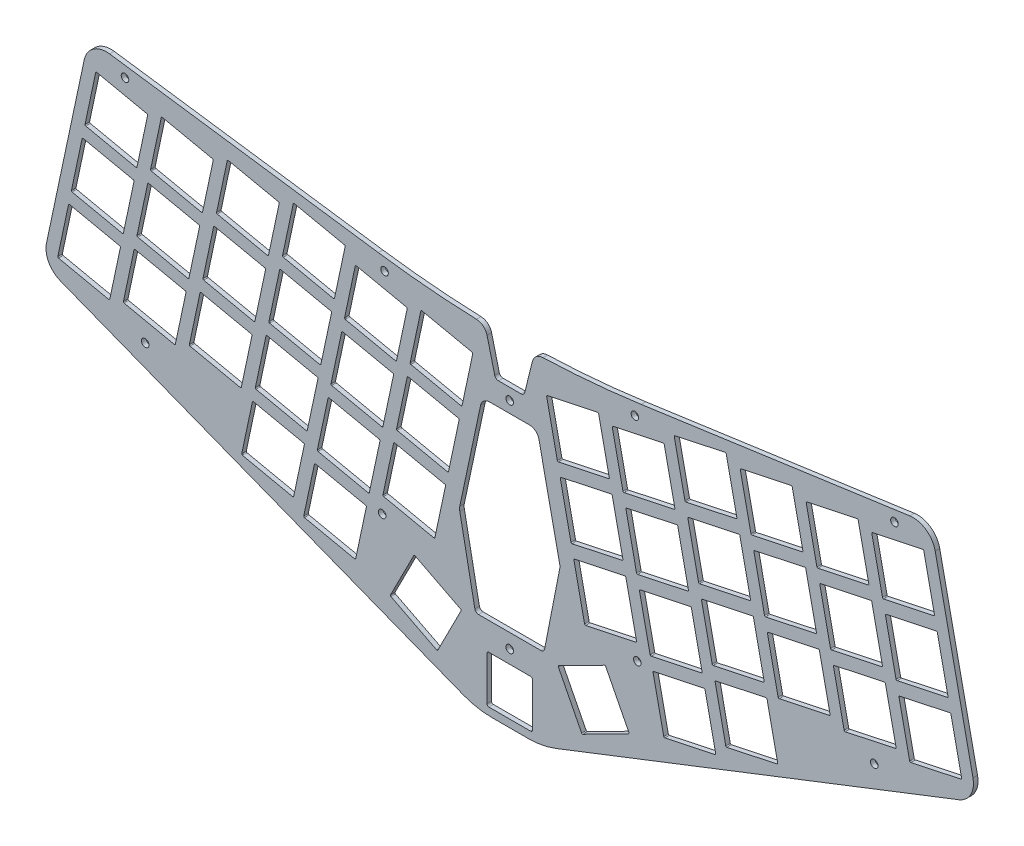
SolidWorks part; units mm, degrees
ref_plane "Front Plane" through (0, 0, 0) normal (0, 0, 1) x (1, 0, 0)
ref_plane "Top Plane" through (0, 0, 0) normal (0, 1, 0) x (1, 0, 0)
ref_plane "Right Plane" through (0, 0, 0) normal (1, 0, 0) x (0, 0, -1)
sketch "Model" plane through (0, 0, 0) normal (0, 0, 1) x (1, 0, 0)
  line L0 (118.9761, -36.3417) -> (119.3386, -36.3417)
  line L1 (109.9761, -36.3417) -> (109.6135, -36.3417)
  line L2 (130.2178, -33.5671) -> (126.6009, -34.9766)
  line L3 (98.7344, -33.5671) -> (102.3512, -34.9766)
  line L4 (114.4761, -36.3417) -> (109.9761, -36.3417)
  line L5 (114.4761, -36.3417) -> (118.9761, -36.3417)
  line L6 (118.4251, 42.1791) -> (120.4508, 50.3035)
  line L7 (110.527, 42.1791) -> (108.5014, 50.3035)
  line L8 (130.2178, -33.5671) -> (232.9153, 6.4558)
  line L9 (236.6055, 13.2938) -> (226.6558, 60.1035)
  line L10 (219.9519, 64.7976) -> (149.1302, 54.8443)
  line L11 (79.822, 54.8443) -> (9.0003, 64.7976)
  line L12 (2.2964, 60.1035) -> (-7.6533, 13.2938)
  line L13 (-3.9631, 6.4558) -> (98.7344, -33.5671)
  line L14 (111.4973, 41.421) -> (117.4548, 41.421)
  line L15 (119.9761, -34.3417) -> (108.9761, -34.3417)
  line L16 (120.4761, -22.3417) -> (120.4761, -33.8417)
  line L17 (108.9761, -21.8417) -> (119.9761, -21.8417)
  line L18 (108.4761, -33.8417) -> (108.4761, -22.3417)
  line L19 (123.6714, -13.7578) -> (127.6435, 6.5155)
  line L20 (105.2808, -13.7578) -> (101.3087, 6.5155)
  line L21 (106.2621, -14.5655) -> (122.69, -14.5655)
  line L22 (109.4761, 35.421) -> (109.2316, 35.421)
  line L23 (119.4761, 35.421) -> (119.7205, 35.421)
  line L24 (109.4761, 35.421) -> (119.4761, 35.421)
  line L25 (127.6339, 7.716) -> (122.1659, 33.4408)
  line L26 (101.3183, 7.716) -> (106.7863, 33.4408)
  line L27 (230.5128, 25.1235) -> (217.3078, 22.3167)
  line L28 (217.1153, 22.0202) -> (219.9221, 8.8152)
  line L29 (220.2186, 8.6226) -> (233.4236, 11.4294)
  line L30 (233.6161, 11.7259) -> (230.8093, 24.9309)
  line L31 (226.9263, 41.9965) -> (213.7213, 39.1897)
  line L32 (213.5288, 38.8932) -> (216.3356, 25.6882)
  line L33 (216.6321, 25.4957) -> (229.8371, 28.3025)
  line L34 (230.0297, 28.599) -> (227.2228, 41.804)
  line L35 (223.3399, 58.8696) -> (210.1349, 56.0628)
  line L36 (209.9423, 55.7663) -> (212.7491, 42.5613)
  line L37 (213.0456, 42.3687) -> (226.2506, 45.1755)
  line L38 (226.4432, 45.472) -> (223.6364, 58.677)
  line L39 (213.2239, 23.4933) -> (200.0189, 20.6865)
  line L40 (199.8264, 20.39) -> (202.6332, 7.185)
  line L41 (202.9297, 6.9924) -> (216.1347, 9.7992)
  line L42 (216.3273, 10.0958) -> (213.5205, 23.3007)
  line L43 (209.6375, 40.3663) -> (196.4325, 37.5595)
  line L44 (196.2399, 37.263) -> (199.0467, 24.058)
  line L45 (199.3432, 23.8655) -> (212.5482, 26.6723)
  line L46 (212.7408, 26.9688) -> (209.934, 40.1738)
  line L47 (206.051, 57.2394) -> (192.846, 54.4326)
  line L48 (192.6534, 54.1361) -> (195.4602, 40.9311)
  line L49 (195.7568, 40.7385) -> (208.9618, 43.5453)
  line L50 (209.1543, 43.8418) -> (206.3475, 57.0468)
  line L51 (195.8311, 22.3522) -> (182.6261, 19.5454)
  line L52 (182.4336, 19.2489) -> (185.2404, 6.0439)
  line L53 (185.5369, 5.8513) -> (198.7419, 8.6581)
  line L54 (198.9344, 8.9546) -> (196.1276, 22.1596)
  line L55 (192.2446, 39.2252) -> (179.0396, 36.4184)
  line L56 (178.8471, 36.1219) -> (181.6539, 22.9169)
  line L57 (181.9504, 22.7244) -> (195.1554, 25.5312)
  line L58 (195.348, 25.8277) -> (192.5412, 39.0327)
  line L59 (188.6582, 56.0983) -> (175.4532, 53.2915)
  line L60 (175.2606, 52.995) -> (178.0674, 39.79)
  line L61 (178.3639, 39.5974) -> (191.5689, 42.4042)
  line L62 (191.7615, 42.7007) -> (188.9547, 55.9057)
  line L63 (182.0248, 4.338) -> (168.8198, 1.5312)
  line L64 (168.6272, 1.2347) -> (171.434, -11.9703)
  line L65 (171.7305, -12.1628) -> (184.9355, -9.356)
  line L66 (185.1281, -9.0595) -> (182.3213, 4.1455)
  line L67 (178.4383, 21.2111) -> (165.2333, 18.4043)
  line L68 (165.0407, 18.1078) -> (167.8475, 4.9028)
  line L69 (168.1441, 4.7102) -> (181.3491, 7.517)
  line L70 (181.5416, 7.8135) -> (178.7348, 21.0185)
  line L71 (174.8518, 38.0841) -> (161.6468, 35.2773)
  line L72 (161.4543, 34.9808) -> (164.2611, 21.7758)
  line L73 (164.5576, 21.5833) -> (177.7626, 24.3901)
  line L74 (177.9551, 24.6866) -> (175.1483, 37.8916)
  line L75 (171.2653, 54.9572) -> (158.0603, 52.1504)
  line L76 (157.8678, 51.8539) -> (160.6746, 38.6489)
  line L77 (160.9711, 38.4563) -> (174.1761, 41.2631)
  line L78 (174.3687, 41.5596) -> (171.5619, 54.7646)
  line L79 (165.6715, -1.6938) -> (152.4665, -4.5006)
  line L80 (152.2739, -4.7971) -> (155.0808, -18.0021)
  line L81 (155.3773, -18.1947) -> (168.5823, -15.3879)
  line L82 (168.7748, -15.0914) -> (165.968, -1.8864)
  line L83 (162.085, 15.1792) -> (148.88, 12.3724)
  line L84 (148.6875, 12.0759) -> (151.4943, -1.1291)
  line L85 (151.7908, -1.3216) -> (164.9958, 1.4852)
  line L86 (165.1883, 1.7817) -> (162.3815, 14.9867)
  line L87 (158.4985, 32.0523) -> (145.2936, 29.2455)
  line L88 (145.101, 28.949) -> (147.9078, 15.744)
  line L89 (148.2043, 15.5514) -> (161.4093, 18.3582)
  line L90 (161.6019, 18.6547) -> (158.7951, 31.8597)
  line L91 (154.9121, 48.9253) -> (141.7071, 46.1185)
  line L92 (141.5145, 45.822) -> (144.3213, 32.617)
  line L93 (144.6178, 32.4245) -> (157.8228, 35.2313)
  line L94 (158.0154, 35.5278) -> (155.2086, 48.7328)
  line L95 (137.6232, 47.2952) -> (124.4182, 44.4883)
  line L96 (124.2256, 44.1918) -> (127.0325, 30.9868)
  line L97 (127.329, 30.7943) -> (140.534, 33.6011)
  line L98 (140.7265, 33.8976) -> (137.9197, 47.1026)
  line L99 (141.2097, 30.4221) -> (128.0047, 27.6153)
  line L100 (127.8121, 27.3188) -> (130.6189, 14.1138)
  line L101 (130.9154, 13.9212) -> (144.1204, 16.728)
  line L102 (144.313, 17.0246) -> (141.5062, 30.2295)
  line L103 (144.7962, 13.5491) -> (131.5912, 10.7423)
  line L104 (131.3986, 10.4457) -> (134.2054, -2.7593)
  line L105 (134.5019, -2.9518) -> (147.7069, -0.145)
  line L106 (147.8995, 0.1515) -> (145.0927, 13.3565)
  line L107 (139.4422, -9.5606) -> (127.4136, -15.6895)
  line L108 (127.3043, -16.0257) -> (133.4332, -28.0543)
  line L109 (133.7695, -28.1635) -> (145.7981, -22.0347)
  line L110 (145.9073, -21.6984) -> (139.7784, -9.6698)
  line L111 (101.5386, -15.6895) -> (89.51, -9.5606)
  line L112 (89.1737, -9.6698) -> (83.0449, -21.6984)
  line L113 (83.1541, -22.0347) -> (95.1827, -28.1635)
  line L114 (95.519, -28.0543) -> (101.6478, -16.0257)
  line L115 (97.361, 10.7423) -> (84.156, 13.5491)
  line L116 (83.8595, 13.3565) -> (81.0527, 0.1515)
  line L117 (81.2453, -0.145) -> (94.4502, -2.9518)
  line L118 (94.7468, -2.7593) -> (97.5536, 10.4457)
  line L119 (100.9475, 27.6153) -> (87.7425, 30.4221)
  line L120 (87.446, 30.2295) -> (84.6392, 17.0246)
  line L121 (84.8317, 16.728) -> (98.0367, 13.9212)
  line L122 (98.3332, 14.1138) -> (101.14, 27.3188)
  line L123 (104.534, 44.4883) -> (91.329, 47.2952)
  line L124 (91.0325, 47.1026) -> (88.2256, 33.8976)
  line L125 (88.4182, 33.6011) -> (101.6232, 30.7943)
  line L126 (101.9197, 30.9868) -> (104.7265, 44.1918)
  line L127 (76.4857, -4.5006) -> (63.2807, -1.6938)
  line L128 (62.9842, -1.8864) -> (60.1773, -15.0914)
  line L129 (60.3699, -15.3879) -> (73.5749, -18.1947)
  line L130 (73.8714, -18.0021) -> (76.6782, -4.7971)
  line L131 (80.0721, 12.3724) -> (66.8671, 15.1792)
  line L132 (66.5706, 14.9867) -> (63.7638, 1.7817)
  line L133 (63.9564, 1.4852) -> (77.1614, -1.3216)
  line L134 (77.4579, -1.1291) -> (80.2647, 12.0759)
  line L135 (83.6586, 29.2455) -> (70.4536, 32.0523)
  line L136 (70.1571, 31.8597) -> (67.3503, 18.6547)
  line L137 (67.5429, 18.3582) -> (80.7479, 15.5514)
  line L138 (81.0444, 15.744) -> (83.8512, 28.949)
  line L139 (87.2451, 46.1185) -> (74.0401, 48.9253)
  line L140 (73.7436, 48.7328) -> (70.9368, 35.5278)
  line L141 (71.1293, 35.2313) -> (84.3343, 32.4245)
  line L142 (84.6308, 32.617) -> (87.4377, 45.822)
  line L143 (60.1324, 1.5312) -> (46.9274, 4.338)
  line L144 (46.6309, 4.1455) -> (43.8241, -9.0595)
  line L145 (44.0166, -9.356) -> (57.2216, -12.1628)
  line L146 (57.5181, -11.9703) -> (60.325, 1.2347)
  line L147 (63.7189, 18.4043) -> (50.5139, 21.2111)
  line L148 (50.2174, 21.0185) -> (47.4106, 7.8135)
  line L149 (47.6031, 7.517) -> (60.8081, 4.7102)
  line L150 (61.1046, 4.9028) -> (63.9114, 18.1078)
  line L151 (67.3054, 35.2773) -> (54.1004, 38.0841)
  line L152 (53.8038, 37.8916) -> (50.997, 24.6866)
  line L153 (51.1896, 24.3901) -> (64.3946, 21.5833)
  line L154 (64.6911, 21.7758) -> (67.4979, 34.9808)
  line L155 (70.8918, 52.1504) -> (57.6868, 54.9572)
  line L156 (57.3903, 54.7646) -> (54.5835, 41.5596)
  line L157 (54.7761, 41.2631) -> (67.9811, 38.4563)
  line L158 (68.2776, 38.6489) -> (71.0844, 51.8539)
  line L159 (46.5186, 19.2489) -> (45.1152, 12.6464)
  line L160 (33.1211, 22.3522) -> (46.326, 19.5454)
  line L161 (30.0177, 8.9546) -> (32.8245, 22.1596)
  line L162 (43.4153, 5.8513) -> (30.2103, 8.6581)
  line L163 (45.1152, 12.6464) -> (43.7118, 6.0439)
  line L164 (50.1051, 36.1219) -> (48.7017, 29.5194)
  line L165 (36.7075, 39.2252) -> (49.9125, 36.4184)
  line L166 (33.6042, 25.8277) -> (36.411, 39.0327)
  line L167 (47.0018, 22.7244) -> (33.7968, 25.5312)
  line L168 (48.7017, 29.5194) -> (47.2983, 22.9169)
  line L169 (53.6916, 52.995) -> (52.2882, 46.3925)
  line L170 (40.294, 56.0983) -> (53.499, 53.2915)
  line L171 (37.1907, 42.7007) -> (39.9975, 55.9057)
  line L172 (50.5882, 39.5974) -> (37.3832, 42.4042)
  line L173 (52.2882, 46.3925) -> (50.8848, 39.79)
  line L174 (29.1258, 20.39) -> (27.7224, 13.7875)
  line L175 (15.7282, 23.4933) -> (28.9332, 20.6865)
  line L176 (12.6249, 10.0958) -> (15.4317, 23.3007)
  line L177 (26.0225, 6.9924) -> (12.8175, 9.7992)
  line L178 (27.7224, 13.7875) -> (26.319, 7.185)
  line L179 (32.7123, 37.263) -> (31.3089, 30.6605)
  line L180 (19.3147, 40.3663) -> (32.5197, 37.5595)
  line L181 (16.2114, 26.9688) -> (19.0182, 40.1738)
  line L182 (29.6089, 23.8655) -> (16.4039, 26.6723)
  line L183 (31.3089, 30.6605) -> (29.9055, 24.058)
  line L184 (19.7979, 43.8418) -> (21.2013, 50.4443)
  line L185 (33.1954, 40.7385) -> (19.9904, 43.5453)
  line L186 (36.2987, 54.1361) -> (33.4919, 40.9311)
  line L187 (22.9012, 57.2394) -> (36.1062, 54.4326)
  line L188 (21.2013, 50.4443) -> (22.6047, 57.0468)
  line L189 (-4.664, 11.7259) -> (-3.2606, 18.3284)
  line L190 (8.7336, 8.6226) -> (-4.4714, 11.4294)
  line L191 (11.8369, 22.0202) -> (9.0301, 8.8152)
  line L192 (-1.5606, 25.1235) -> (11.6444, 22.3167)
  line L193 (-3.2606, 18.3284) -> (-1.8572, 24.9309)
  line L194 (15.2308, 39.1897) -> (8.6283, 40.5931)
  line L195 (12.6166, 25.6882) -> (15.4234, 38.8932)
  line L196 (-0.8849, 28.3025) -> (12.3201, 25.4957)
  line L197 (1.7293, 41.804) -> (-1.0775, 28.599)
  line L198 (8.6283, 40.5931) -> (2.0258, 41.9965)
  line L199 (2.509, 45.472) -> (3.9124, 52.0745)
  line L200 (15.9065, 42.3687) -> (2.7016, 45.1755)
  line L201 (19.0099, 55.7663) -> (16.2031, 42.5613)
  line L202 (5.6123, 58.8696) -> (18.8173, 56.0628)
  line L203 (3.9124, 52.0745) -> (5.3158, 58.677)
  circle A0 centre (215.9057, 61.3788) radius 1
  circle A1 centre (13.0465, 61.3788) radius 1
  circle A2 centre (148.1114, -4.3098) radius 1
  circle A3 centre (80.8407, -4.3098) radius 1
  circle A4 centre (210.5718, 3.5051) radius 1
  circle A5 centre (147.4779, 51.4345) radius 1
  circle A6 centre (81.4742, 51.4345) radius 1
  circle A7 centre (18.3804, 3.5051) radius 1
  circle A8 centre (114.4761, -18.3417) radius 1
  circle A9 centre (114.4761, 38.421) radius 1
  arc A10 (108.4761, -33.8417) -> (108.9761, -34.3417) centre (108.9761, -33.8417) ccw
  arc A11 (119.9761, -34.3417) -> (120.4761, -33.8417) centre (119.9761, -33.8417) ccw
  arc A12 (120.4761, -22.3417) -> (119.9761, -21.8417) centre (119.9761, -22.3417) ccw
  arc A13 (108.9761, -21.8417) -> (108.4761, -22.3417) centre (108.9761, -22.3417) ccw
  arc A14 (122.69, -14.5655) -> (123.6714, -13.7578) centre (122.69, -13.5655) ccw
  arc A15 (105.2808, -13.7578) -> (106.2621, -14.5655) centre (106.2621, -13.5655) ccw
  arc A16 (127.6435, 6.5155) -> (127.6339, 7.716) centre (124.6994, 7.0923) ccw
  arc A17 (101.3183, 7.716) -> (101.3087, 6.5155) centre (104.2527, 7.0923) ccw
  arc A18 (122.1659, 33.4408) -> (119.7205, 35.421) centre (119.7205, 32.921) ccw
  arc A19 (109.2316, 35.421) -> (106.7863, 33.4408) centre (109.2316, 32.921) ccw
  arc A20 (46.5186, 19.2489) -> (46.326, 19.5454) centre (46.2741, 19.3008) ccw
  arc A21 (30.0177, 8.9546) -> (30.2103, 8.6581) centre (30.2623, 8.9027) ccw
  arc A22 (33.1211, 22.3522) -> (32.8245, 22.1596) centre (33.0691, 22.1077) ccw
  arc A23 (43.4153, 5.8513) -> (43.7118, 6.0439) centre (43.4673, 6.0959) ccw
  arc A24 (50.1051, 36.1219) -> (49.9125, 36.4184) centre (49.8605, 36.1739) ccw
  arc A25 (36.7075, 39.2252) -> (36.411, 39.0327) centre (36.6556, 38.9807) ccw
  arc A26 (33.6042, 25.8277) -> (33.7968, 25.5312) centre (33.8487, 25.7757) ccw
  arc A27 (47.0018, 22.7244) -> (47.2983, 22.9169) centre (47.0537, 22.9689) ccw
  arc A28 (53.6916, 52.995) -> (53.499, 53.2915) centre (53.447, 53.0469) ccw
  arc A29 (40.294, 56.0983) -> (39.9975, 55.9057) centre (40.242, 55.8537) ccw
  arc A30 (37.1907, 42.7007) -> (37.3832, 42.4042) centre (37.4352, 42.6488) ccw
  arc A31 (50.5882, 39.5974) -> (50.8848, 39.79) centre (50.6402, 39.8419) ccw
  arc A32 (29.1258, 20.39) -> (28.9332, 20.6865) centre (28.8812, 20.442) ccw
  arc A33 (15.7282, 23.4933) -> (15.4317, 23.3007) centre (15.6763, 23.2488) ccw
  arc A34 (12.6249, 10.0958) -> (12.8175, 9.7992) centre (12.8694, 10.0438) ccw
  arc A35 (26.0225, 6.9924) -> (26.319, 7.185) centre (26.0744, 7.237) ccw
  arc A36 (19.3147, 40.3663) -> (19.0182, 40.1738) centre (19.2627, 40.1218) ccw
  arc A37 (32.7123, 37.263) -> (32.5197, 37.5595) centre (32.4677, 37.315) ccw
  arc A38 (16.2114, 26.9688) -> (16.4039, 26.6723) centre (16.4559, 26.9168) ccw
  arc A39 (29.6089, 23.8655) -> (29.9055, 24.058) centre (29.6609, 24.11) ccw
  arc A40 (19.7979, 43.8418) -> (19.9904, 43.5453) centre (20.0424, 43.7899) ccw
  arc A41 (36.2987, 54.1361) -> (36.1062, 54.4326) centre (36.0542, 54.188) ccw
  arc A42 (33.1954, 40.7385) -> (33.4919, 40.9311) centre (33.2474, 40.9831) ccw
  arc A43 (22.9012, 57.2394) -> (22.6047, 57.0468) centre (22.8492, 56.9949) ccw
  arc A44 (-4.664, 11.7259) -> (-4.4714, 11.4294) centre (-4.4194, 11.674) ccw
  arc A45 (11.8369, 22.0202) -> (11.6444, 22.3167) centre (11.5924, 22.0721) ccw
  arc A46 (8.7336, 8.6226) -> (9.0301, 8.8152) centre (8.7856, 8.8671) ccw
  arc A47 (-1.5606, 25.1235) -> (-1.8572, 24.9309) centre (-1.6126, 24.8789) ccw
  arc A48 (15.4234, 38.8932) -> (15.2308, 39.1897) centre (15.1789, 38.9452) ccw
  arc A49 (12.3201, 25.4957) -> (12.6166, 25.6882) centre (12.372, 25.7402) ccw
  arc A50 (-1.0775, 28.599) -> (-0.8849, 28.3025) centre (-0.8329, 28.547) ccw
  arc A51 (2.0258, 41.9965) -> (1.7293, 41.804) centre (1.9739, 41.752) ccw
  arc A52 (2.509, 45.472) -> (2.7016, 45.1755) centre (2.7535, 45.42) ccw
  arc A53 (19.0099, 55.7663) -> (18.8173, 56.0628) centre (18.7653, 55.8182) ccw
  arc A54 (15.9065, 42.3687) -> (16.2031, 42.5613) centre (15.9585, 42.6132) ccw
  arc A55 (5.6123, 58.8696) -> (5.3158, 58.677) centre (5.5603, 58.625) ccw
  arc A56 (102.3512, -34.9766) -> (109.6135, -36.3417) centre (109.6135, -16.3417) ccw
  arc A57 (119.3386, -36.3417) -> (126.6009, -34.9766) centre (119.3386, -16.3417) ccw
  arc A58 (108.5014, 50.3035) -> (105.6963, 52.5758) centre (105.5905, 49.5777) ccw
  arc A59 (123.2559, 52.5758) -> (120.4508, 50.3035) centre (123.3617, 49.5777) ccw
  arc A60 (117.4548, 41.421) -> (118.4251, 42.1791) centre (117.4548, 42.421) ccw
  arc A61 (110.527, 42.1791) -> (111.4973, 41.421) centre (111.4973, 42.421) ccw
  arc A62 (232.9153, 6.4558) -> (236.6055, 13.2938) centre (230.7366, 12.0463) ccw
  arc A63 (226.6558, 60.1035) -> (219.9519, 64.7976) centre (220.7869, 58.856) ccw
  arc A64 (123.2559, 52.5758) -> (149.1302, 54.8443) centre (114.4761, 301.421) ccw
  arc A65 (79.822, 54.8443) -> (105.6963, 52.5758) centre (114.4761, 301.421) ccw
  arc A66 (9.0003, 64.7976) -> (2.2964, 60.1035) centre (8.1653, 58.856) ccw
  arc A67 (-7.6533, 13.2938) -> (-3.9631, 6.4558) centre (-1.7844, 12.0463) ccw
  arc A68 (217.3078, 22.3167) -> (217.1153, 22.0202) centre (217.3598, 22.0721) ccw
  arc A69 (219.9221, 8.8152) -> (220.2186, 8.6226) centre (220.1666, 8.8671) ccw
  arc A70 (233.4236, 11.4294) -> (233.6161, 11.7259) centre (233.3716, 11.674) ccw
  arc A71 (230.8093, 24.9309) -> (230.5128, 25.1235) centre (230.5648, 24.8789) ccw
  arc A72 (213.7213, 39.1897) -> (213.5288, 38.8932) centre (213.7733, 38.9452) ccw
  arc A73 (216.3356, 25.6882) -> (216.6321, 25.4957) centre (216.5801, 25.7402) ccw
  arc A74 (229.8371, 28.3025) -> (230.0297, 28.599) centre (229.7851, 28.547) ccw
  arc A75 (227.2228, 41.804) -> (226.9263, 41.9965) centre (226.9783, 41.752) ccw
  arc A76 (210.1349, 56.0628) -> (209.9423, 55.7663) centre (210.1868, 55.8182) ccw
  arc A77 (212.7491, 42.5613) -> (213.0456, 42.3687) centre (212.9937, 42.6132) ccw
  arc A78 (226.2506, 45.1755) -> (226.4432, 45.472) centre (226.1986, 45.42) ccw
  arc A79 (223.6364, 58.677) -> (223.3399, 58.8696) centre (223.3918, 58.625) ccw
  arc A80 (200.0189, 20.6865) -> (199.8264, 20.39) centre (200.0709, 20.442) ccw
  arc A81 (202.6332, 7.185) -> (202.9297, 6.9924) centre (202.8777, 7.237) ccw
  arc A82 (216.1347, 9.7992) -> (216.3273, 10.0958) centre (216.0827, 10.0438) ccw
  arc A83 (213.5205, 23.3007) -> (213.2239, 23.4933) centre (213.2759, 23.2488) ccw
  arc A84 (196.4325, 37.5595) -> (196.2399, 37.263) centre (196.4845, 37.315) ccw
  arc A85 (199.0467, 24.058) -> (199.3432, 23.8655) centre (199.2913, 24.11) ccw
  arc A86 (212.5482, 26.6723) -> (212.7408, 26.9688) centre (212.4963, 26.9168) ccw
  arc A87 (209.934, 40.1738) -> (209.6375, 40.3663) centre (209.6894, 40.1218) ccw
  arc A88 (192.846, 54.4326) -> (192.6534, 54.1361) centre (192.898, 54.188) ccw
  arc A89 (195.4602, 40.9311) -> (195.7568, 40.7385) centre (195.7048, 40.9831) ccw
  arc A90 (208.9618, 43.5453) -> (209.1543, 43.8418) centre (208.9098, 43.7899) ccw
  arc A91 (206.3475, 57.0468) -> (206.051, 57.2394) centre (206.103, 56.9949) ccw
  arc A92 (182.6261, 19.5454) -> (182.4336, 19.2489) centre (182.6781, 19.3008) ccw
  arc A93 (185.2404, 6.0439) -> (185.5369, 5.8513) centre (185.4849, 6.0959) ccw
  arc A94 (198.7419, 8.6581) -> (198.9344, 8.9546) centre (198.6899, 8.9027) ccw
  arc A95 (196.1276, 22.1596) -> (195.8311, 22.3522) centre (195.8831, 22.1077) ccw
  arc A96 (179.0396, 36.4184) -> (178.8471, 36.1219) centre (179.0916, 36.1739) ccw
  arc A97 (181.6539, 22.9169) -> (181.9504, 22.7244) centre (181.8984, 22.9689) ccw
  arc A98 (195.1554, 25.5312) -> (195.348, 25.8277) centre (195.1034, 25.7757) ccw
  arc A99 (192.5412, 39.0327) -> (192.2446, 39.2252) centre (192.2966, 38.9807) ccw
  arc A100 (175.4532, 53.2915) -> (175.2606, 52.995) centre (175.5051, 53.0469) ccw
  arc A101 (178.0674, 39.79) -> (178.3639, 39.5974) centre (178.312, 39.8419) ccw
  arc A102 (191.5689, 42.4042) -> (191.7615, 42.7007) centre (191.5169, 42.6488) ccw
  arc A103 (188.9547, 55.9057) -> (188.6582, 56.0983) centre (188.7101, 55.8537) ccw
  arc A104 (168.8198, 1.5312) -> (168.6272, 1.2347) centre (168.8718, 1.2867) ccw
  arc A105 (171.434, -11.9703) -> (171.7305, -12.1628) centre (171.6786, -11.9183) ccw
  arc A106 (184.9355, -9.356) -> (185.1281, -9.0595) centre (184.8836, -9.1115) ccw
  arc A107 (182.3213, 4.1455) -> (182.0248, 4.338) centre (182.0767, 4.0935) ccw
  arc A108 (165.2333, 18.4043) -> (165.0407, 18.1078) centre (165.2853, 18.1597) ccw
  arc A109 (167.8475, 4.9028) -> (168.1441, 4.7102) centre (168.0921, 4.9547) ccw
  arc A110 (181.3491, 7.517) -> (181.5416, 7.8135) centre (181.2971, 7.7616) ccw
  arc A111 (178.7348, 21.0185) -> (178.4383, 21.2111) centre (178.4903, 20.9665) ccw
  arc A112 (161.6468, 35.2773) -> (161.4543, 34.9808) centre (161.6988, 35.0328) ccw
  arc A113 (164.2611, 21.7758) -> (164.5576, 21.5833) centre (164.5056, 21.8278) ccw
  arc A114 (177.7626, 24.3901) -> (177.9551, 24.6866) centre (177.7106, 24.6346) ccw
  arc A115 (175.1483, 37.8916) -> (174.8518, 38.0841) centre (174.9038, 37.8396) ccw
  arc A116 (158.0603, 52.1504) -> (157.8678, 51.8539) centre (158.1123, 51.9058) ccw
  arc A117 (160.6746, 38.6489) -> (160.9711, 38.4563) centre (160.9191, 38.7008) ccw
  arc A118 (174.1761, 41.2631) -> (174.3687, 41.5596) centre (174.1241, 41.5076) ccw
  arc A119 (171.5619, 54.7646) -> (171.2653, 54.9572) centre (171.3173, 54.7126) ccw
  arc A120 (152.4665, -4.5006) -> (152.2739, -4.7971) centre (152.5185, -4.7452) ccw
  arc A121 (155.0808, -18.0021) -> (155.3773, -18.1947) centre (155.3253, -17.9501) ccw
  arc A122 (168.5823, -15.3879) -> (168.7748, -15.0914) centre (168.5303, -15.1433) ccw
  arc A123 (165.968, -1.8864) -> (165.6715, -1.6938) centre (165.7235, -1.9383) ccw
  arc A124 (148.88, 12.3724) -> (148.6875, 12.0759) centre (148.932, 12.1279) ccw
  arc A125 (151.4943, -1.1291) -> (151.7908, -1.3216) centre (151.7388, -1.0771) ccw
  arc A126 (164.9958, 1.4852) -> (165.1883, 1.7817) centre (164.9438, 1.7297) ccw
  arc A127 (162.3815, 14.9867) -> (162.085, 15.1792) centre (162.137, 14.9347) ccw
  arc A128 (145.2936, 29.2455) -> (145.101, 28.949) centre (145.3455, 29.0009) ccw
  arc A129 (147.9078, 15.744) -> (148.2043, 15.5514) centre (148.1523, 15.7959) ccw
  arc A130 (161.4093, 18.3582) -> (161.6019, 18.6547) centre (161.3573, 18.6028) ccw
  arc A131 (158.7951, 31.8597) -> (158.4985, 32.0523) centre (158.5505, 31.8078) ccw
  arc A132 (141.7071, 46.1185) -> (141.5145, 45.822) centre (141.7591, 45.874) ccw
  arc A133 (144.3213, 32.617) -> (144.6178, 32.4245) centre (144.5659, 32.669) ccw
  arc A134 (157.8228, 35.2313) -> (158.0154, 35.5278) centre (157.7709, 35.4758) ccw
  arc A135 (155.2086, 48.7328) -> (154.9121, 48.9253) centre (154.964, 48.6808) ccw
  arc A136 (124.4182, 44.4883) -> (124.2256, 44.1918) centre (124.4702, 44.2438) ccw
  arc A137 (127.0325, 30.9868) -> (127.329, 30.7943) centre (127.277, 31.0388) ccw
  arc A138 (140.534, 33.6011) -> (140.7265, 33.8976) centre (140.482, 33.8456) ccw
  arc A139 (137.9197, 47.1026) -> (137.6232, 47.2952) centre (137.6752, 47.0506) ccw
  arc A140 (128.0047, 27.6153) -> (127.8121, 27.3188) centre (128.0567, 27.3708) ccw
  arc A141 (130.6189, 14.1138) -> (130.9154, 13.9212) centre (130.8635, 14.1658) ccw
  arc A142 (144.1204, 16.728) -> (144.313, 17.0246) centre (144.0685, 16.9726) ccw
  arc A143 (141.5062, 30.2295) -> (141.2097, 30.4221) centre (141.2617, 30.1776) ccw
  arc A144 (131.5912, 10.7423) -> (131.3986, 10.4457) centre (131.6431, 10.4977) ccw
  arc A145 (134.2054, -2.7593) -> (134.5019, -2.9518) centre (134.4499, -2.7073) ccw
  arc A146 (147.7069, -0.145) -> (147.8995, 0.1515) centre (147.6549, 0.0995) ccw
  arc A147 (145.0927, 13.3565) -> (144.7962, 13.5491) centre (144.8481, 13.3045) ccw
  arc A148 (127.4136, -15.6895) -> (127.3043, -16.0257) centre (127.5271, -15.9122) ccw
  arc A149 (133.4332, -28.0543) -> (133.7695, -28.1635) centre (133.656, -27.9408) ccw
  arc A150 (145.7981, -22.0347) -> (145.9073, -21.6984) centre (145.6846, -21.8119) ccw
  arc A151 (139.7784, -9.6698) -> (139.4422, -9.5606) centre (139.5557, -9.7833) ccw
  arc A152 (89.51, -9.5606) -> (89.1737, -9.6698) centre (89.3965, -9.7833) ccw
  arc A153 (83.0449, -21.6984) -> (83.1541, -22.0347) centre (83.2676, -21.8119) ccw
  arc A154 (95.1827, -28.1635) -> (95.519, -28.0543) centre (95.2962, -27.9408) ccw
  arc A155 (101.6478, -16.0257) -> (101.5386, -15.6895) centre (101.4251, -15.9122) ccw
  arc A156 (84.156, 13.5491) -> (83.8595, 13.3565) centre (84.104, 13.3045) ccw
  arc A157 (81.0527, 0.1515) -> (81.2453, -0.145) centre (81.2972, 0.0995) ccw
  arc A158 (94.4502, -2.9518) -> (94.7468, -2.7593) centre (94.5022, -2.7073) ccw
  arc A159 (97.5536, 10.4457) -> (97.361, 10.7423) centre (97.309, 10.4977) ccw
  arc A160 (87.7425, 30.4221) -> (87.446, 30.2295) centre (87.6905, 30.1776) ccw
  arc A161 (84.6392, 17.0246) -> (84.8317, 16.728) centre (84.8837, 16.9726) ccw
  arc A162 (98.0367, 13.9212) -> (98.3332, 14.1138) centre (98.0887, 14.1658) ccw
  arc A163 (101.14, 27.3188) -> (100.9475, 27.6153) centre (100.8955, 27.3708) ccw
  arc A164 (91.329, 47.2952) -> (91.0325, 47.1026) centre (91.277, 47.0506) ccw
  arc A165 (88.2256, 33.8976) -> (88.4182, 33.6011) centre (88.4702, 33.8456) ccw
  arc A166 (101.6232, 30.7943) -> (101.9197, 30.9868) centre (101.6752, 31.0388) ccw
  arc A167 (104.7265, 44.1918) -> (104.534, 44.4883) centre (104.482, 44.2438) ccw
  arc A168 (63.2807, -1.6938) -> (62.9842, -1.8864) centre (63.2287, -1.9383) ccw
  arc A169 (60.1773, -15.0914) -> (60.3699, -15.3879) centre (60.4219, -15.1433) ccw
  arc A170 (73.5749, -18.1947) -> (73.8714, -18.0021) centre (73.6269, -17.9501) ccw
  arc A171 (76.6782, -4.7971) -> (76.4857, -4.5006) centre (76.4337, -4.7452) ccw
  arc A172 (66.8671, 15.1792) -> (66.5706, 14.9867) centre (66.8152, 14.9347) ccw
  arc A173 (63.7638, 1.7817) -> (63.9564, 1.4852) centre (64.0084, 1.7297) ccw
  arc A174 (77.1614, -1.3216) -> (77.4579, -1.1291) centre (77.2134, -1.0771) ccw
  arc A175 (80.2647, 12.0759) -> (80.0721, 12.3724) centre (80.0202, 12.1279) ccw
  arc A176 (70.4536, 32.0523) -> (70.1571, 31.8597) centre (70.4016, 31.8078) ccw
  arc A177 (67.3503, 18.6547) -> (67.5429, 18.3582) centre (67.5948, 18.6028) ccw
  arc A178 (80.7479, 15.5514) -> (81.0444, 15.744) centre (80.7998, 15.7959) ccw
  arc A179 (83.8512, 28.949) -> (83.6586, 29.2455) centre (83.6066, 29.0009) ccw
  arc A180 (74.0401, 48.9253) -> (73.7436, 48.7328) centre (73.9881, 48.6808) ccw
  arc A181 (70.9368, 35.5278) -> (71.1293, 35.2313) centre (71.1813, 35.4758) ccw
  arc A182 (84.3343, 32.4245) -> (84.6308, 32.617) centre (84.3863, 32.669) ccw
  arc A183 (87.4377, 45.822) -> (87.2451, 46.1185) centre (87.1931, 45.874) ccw
  arc A184 (46.9274, 4.338) -> (46.6309, 4.1455) centre (46.8754, 4.0935) ccw
  arc A185 (43.8241, -9.0595) -> (44.0166, -9.356) centre (44.0686, -9.1115) ccw
  arc A186 (57.2216, -12.1628) -> (57.5181, -11.9703) centre (57.2736, -11.9183) ccw
  arc A187 (60.325, 1.2347) -> (60.1324, 1.5312) centre (60.0804, 1.2867) ccw
  arc A188 (50.5139, 21.2111) -> (50.2174, 21.0185) centre (50.4619, 20.9665) ccw
  arc A189 (47.4106, 7.8135) -> (47.6031, 7.517) centre (47.6551, 7.7616) ccw
  arc A190 (60.8081, 4.7102) -> (61.1046, 4.9028) centre (60.8601, 4.9547) ccw
  arc A191 (63.9114, 18.1078) -> (63.7189, 18.4043) centre (63.6669, 18.1597) ccw
  arc A192 (54.1004, 38.0841) -> (53.8038, 37.8916) centre (54.0484, 37.8396) ccw
  arc A193 (50.997, 24.6866) -> (51.1896, 24.3901) centre (51.2416, 24.6346) ccw
  arc A194 (64.3946, 21.5833) -> (64.6911, 21.7758) centre (64.4466, 21.8278) ccw
  arc A195 (67.4979, 34.9808) -> (67.3054, 35.2773) centre (67.2534, 35.0328) ccw
  arc A196 (57.6868, 54.9572) -> (57.3903, 54.7646) centre (57.6349, 54.7126) ccw
  arc A197 (54.5835, 41.5596) -> (54.7761, 41.2631) centre (54.828, 41.5076) ccw
  arc A198 (67.9811, 38.4563) -> (68.2776, 38.6489) centre (68.033, 38.7008) ccw
  arc A199 (71.0844, 51.8539) -> (70.8918, 52.1504) centre (70.8399, 51.9058) ccw
extrude "Boss-Extrude1" add sketch "Model" along normal blind 1.2
